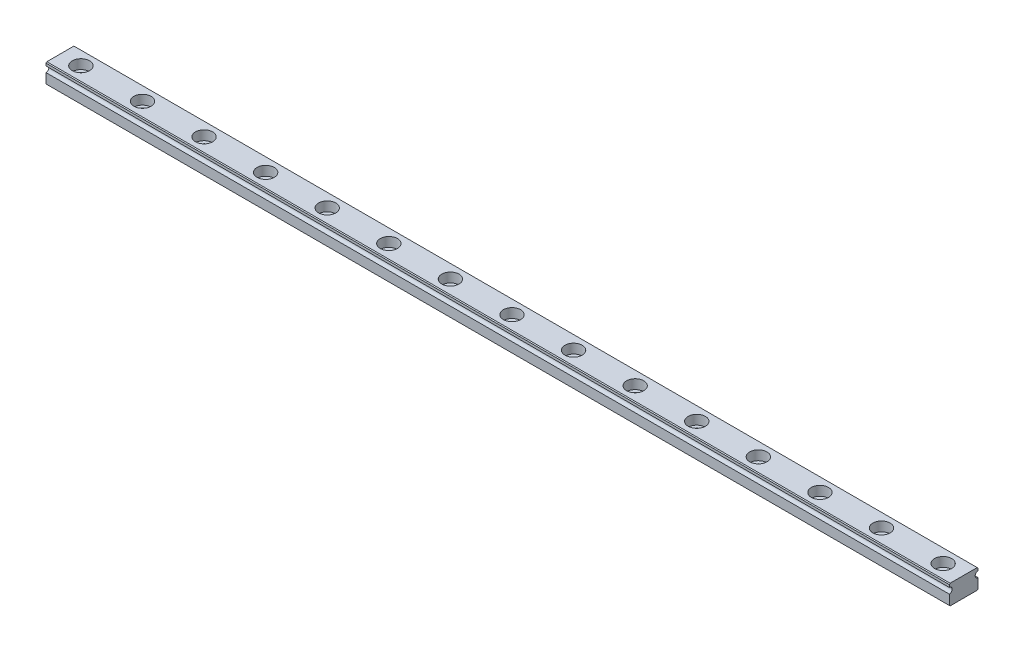
SolidWorks part; units mm, degrees
ref_plane "前视基准面" through (0, 0, 0) normal (0, 0, 1) x (1, 0, 0)
ref_plane "上视基准面" through (0, 0, 0) normal (0, 1, 0) x (1, 0, 0)
ref_plane "右视基准面" through (0, 0, 0) normal (1, 0, 0) x (0, 0, -1)
sketch "草图1" plane through (0, 0, 0) normal (1, 0, 0) x (0, 0, -1)
  line L0 (0, 0) -> (0, 3.6487) construction
  line L1 (0, 0) -> (3.5451, 0) construction
  line L2 (3.498, 0.202) -> (3.498, -2.198)
  line L3 (3.498, -2.198) -> (3.3, -2.396)
  line L4 (3.3, -2.396) -> (-3.3, -2.396)
  line L5 (-3.3, 2.4) -> (3.3, 2.4)
  line L6 (3.3, 2.4) -> (3.498, 2.202)
  line L7 (3.498, 2.202) -> (3.498, 1.602)
  line L8 (-3.498, -2.198) -> (-3.3, -2.396)
  line L9 (-3.498, 0.202) -> (-3.498, -2.198)
  line L10 (-3.498, 2.202) -> (-3.498, 1.602)
  line L11 (-3.3, 2.4) -> (-3.498, 2.202)
  arc A0 (3.498, 1.602) -> (3.498, 0.202) centre (3.498, 0.902) ccw
  arc A1 (-3.498, 1.602) -> (-3.498, 0.202) centre (-3.498, 0.902) cw
  circle A2 centre (0, 0) radius 4.5 construction
  point P17 (0, -2.396)
  point P23 (0, 2.4)
  dimension "D2" = 0.7
  dimension "D10" = 9
  dimension "D1" = 3.3
  dimension "D3" = 2.4
  dimension "D4" = 0.6
  dimension "D5" = 0.28
  dimension "D6" = 135
  dimension "D7" = 0.28
  dimension "D8" = 135
  dimension "D9" = 2.4
extrude "凸台-拉伸1" add sketch "草图1" along normal blind 220
sketch "草图2" plane through (0, 2.4, 0) normal (0, 1, 0) x (1, 0, 0)
  line L0 (0, 0) -> (-4.1171, 0) construction
  line L1 (0, 3.3) -> (0, -3.3) construction
  circle A0 centre (5, 0) radius 2.1
  circle A1 centre (20, 0) radius 2.1
  circle A2 centre (35, 0) radius 2.1
  circle A3 centre (50, 0) radius 2.1
  circle A4 centre (65, 0) radius 2.1
  circle A5 centre (80, 0) radius 2.1
  circle A6 centre (95, 0) radius 2.1
  circle A7 centre (110, 0) radius 2.1
  circle A8 centre (125, 0) radius 2.1
  circle A9 centre (140, 0) radius 2.1
  circle A10 centre (155, 0) radius 2.1
  circle A11 centre (170, 0) radius 2.1
  circle A12 centre (185, 0) radius 2.1
  circle A13 centre (200, 0) radius 2.1
  circle A14 centre (215, 0) radius 2.1
  dimension "D1" = 4.2
  dimension "D2" = 5
  dimension "D3" = 15
extrude "切除-拉伸1" cut sketch "草图2" against normal blind 2.3
sketch "草图3" plane through (0, 2.4, 0) normal (0, 1, 0) x (1, 0, 0)
  circle A0 centre (5, 0) radius 1.2
  circle A1 centre (5, 0) radius 2.1 construction
  circle A2 centre (20, 0) radius 1.2
  circle A3 centre (35, 0) radius 1.2
  circle A4 centre (50, 0) radius 1.2
  circle A5 centre (65, 0) radius 1.2
  circle A6 centre (80, 0) radius 1.2
  circle A7 centre (95, 0) radius 1.2
  circle A8 centre (110, 0) radius 1.2
  circle A9 centre (125, 0) radius 1.2
  circle A10 centre (140, 0) radius 1.2
  circle A11 centre (155, 0) radius 1.2
  circle A12 centre (170, 0) radius 1.2
  circle A13 centre (185, 0) radius 1.2
  circle A14 centre (200, 0) radius 1.2
  circle A15 centre (215, 0) radius 1.2
  dimension "D1" = 2.4
  dimension "D2" = 15
extrude "切除-拉伸2" cut sketch "草图3" against normal through all both and the other way through all
